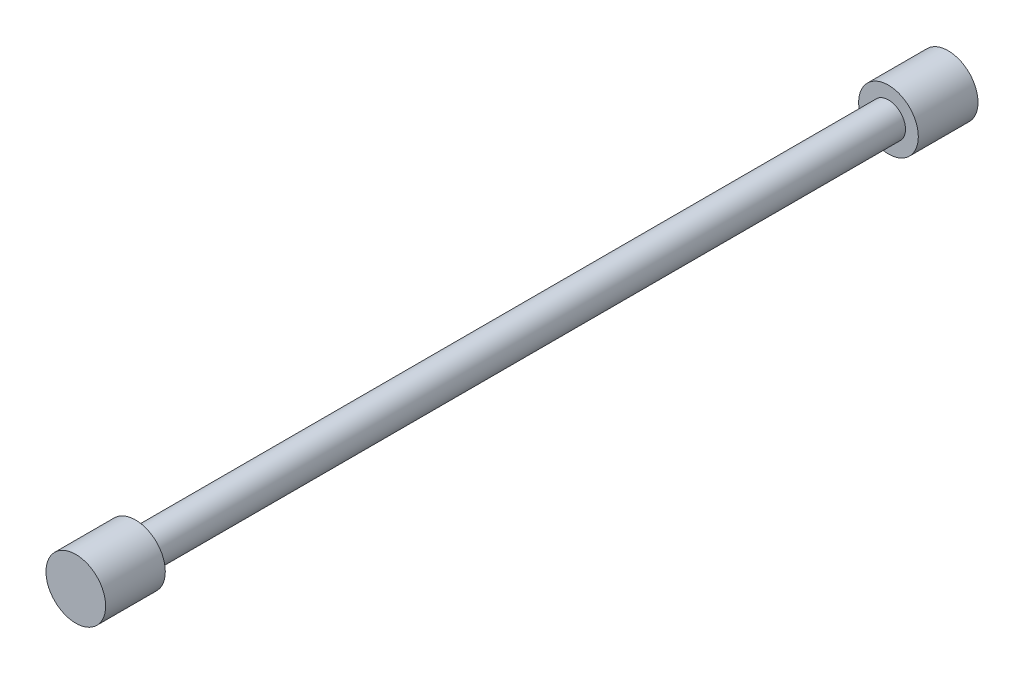
SolidWorks part; units mm, degrees
ref_plane "Front Plane" through (0, 0, 0) normal (0, 0, 1) x (1, 0, 0)
ref_plane "Top Plane" through (0, 0, 0) normal (0, 1, 0) x (1, 0, 0)
ref_plane "Right Plane" through (0, 0, 0) normal (1, 0, 0) x (0, 0, -1)
sketch "SK_Rod" plane through (0, 0, 0) normal (0, 1, 0) x (1, 0, 0)
  line L0 (0, -10) -> (0, 200.641) construction
  line L1 (0, -7) -> (7, -7)
  line L2 (7, -7) -> (7, 7)
  line L3 (7, 7) -> (4, 7)
  line L4 (4, 7) -> (4, 183.641)
  line L5 (4, 183.641) -> (7, 183.641)
  line L6 (7, 183.641) -> (7, 197.641)
  line L7 (7, 197.641) -> (0, 197.641)
  line L8 (0, 197.641) -> (0, -7)
  dimension "P1" = 10
  dimension "P2" = 200.641
  dimension "P3" = 7
  dimension "P4" = 7
  dimension "P5" = 7
  dimension "P6" = 7
  dimension "P7" = 7
  dimension "P8" = 4
  dimension "P9" = 7
  dimension "P10" = 4
  dimension "P11" = 183.641
  dimension "P12" = 7
  dimension "P13" = 183.641
  dimension "P14" = 7
  dimension "P15" = 197.641
  dimension "P16" = 197.641
revolve "Rod_Body" add sketch "SK_Rod" angle 360 about L0
sketch "SK_Ends" plane through (0, 0, 0) normal (0, 1, 0) x (1, 0, 0)
  point P0 (0, 0)
  point P2 (0, 190.641)
  dimension "P1" = 190.641
equation "\"Rod_length\" = 190.641"
